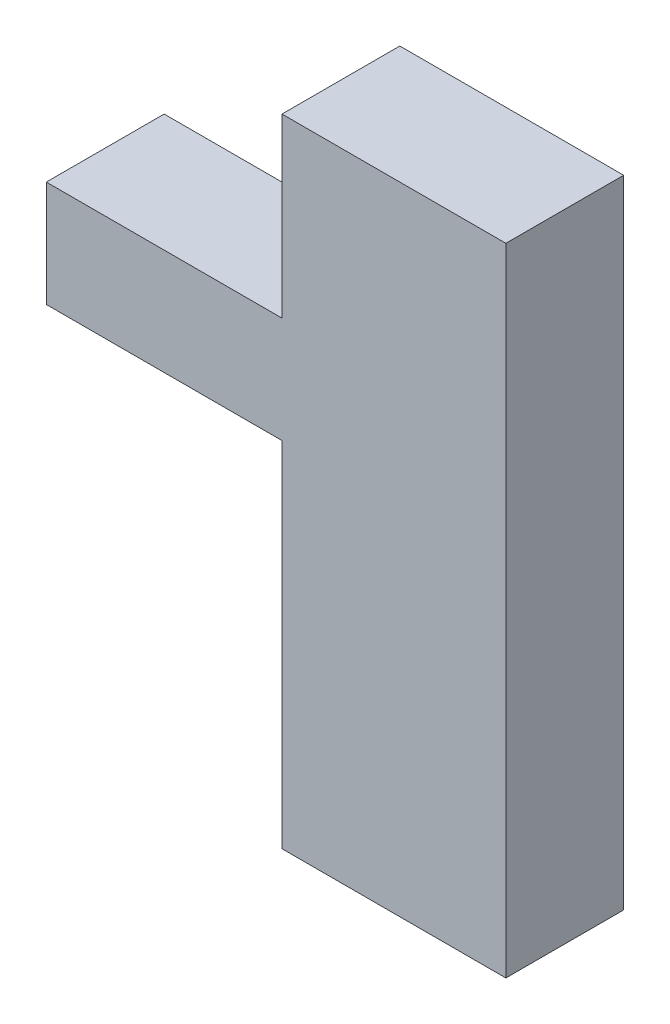
SolidWorks part; units mm, degrees
ref_plane "Front Plane" through (0, 0, 0) normal (0, 0, 1) x (1, 0, 0)
ref_plane "Top Plane" through (0, 0, 0) normal (0, 1, 0) x (1, 0, 0)
ref_plane "Right Plane" through (0, 0, 0) normal (1, 0, 0) x (0, 0, -1)
sketch "Sketch1" plane through (0, 0, 0) normal (0, 0, 1) x (1, 0, 0)
  line L0 (0, 16) -> (0, 22) construction
  line L1 (0, 0) -> (8, 0) construction
  line L2 (0, 0) -> (0, 12) construction
  line L3 (0, 22) -> (8, 22) construction
  line L4 (8, 0) -> (8, 22) construction
  line L5 (0, 16) -> (-8, 16) construction
  line L7 (0, 12) -> (-8, 12) construction
  line L8 (-8, 16) -> (-8, 12) construction
  line L9 (0.2, 0.2) -> (7.8, 0.2)
  line L10 (7.8, 0.2) -> (7.8, 21.8)
  line L11 (0.2, 21.8) -> (7.8, 21.8)
  line L12 (0.2, 15.8) -> (0.2, 21.8)
  line L13 (0.2, 15.8) -> (-7.8, 15.8)
  line L14 (-7.8, 15.8) -> (-7.8, 12.2)
  line L15 (0.2, 12.2) -> (-7.8, 12.2)
  line L16 (0.2, 0.2) -> (0.2, 12.2)
  dimension "D1" = 22
  dimension "D2" = 6
  dimension "D3" = 8
  dimension "D4" = 8
  dimension "D5" = 4
  dimension "D6" = 0.2
extrude "Boss-Extrude1" add sketch "Sketch1" along normal blind 4
